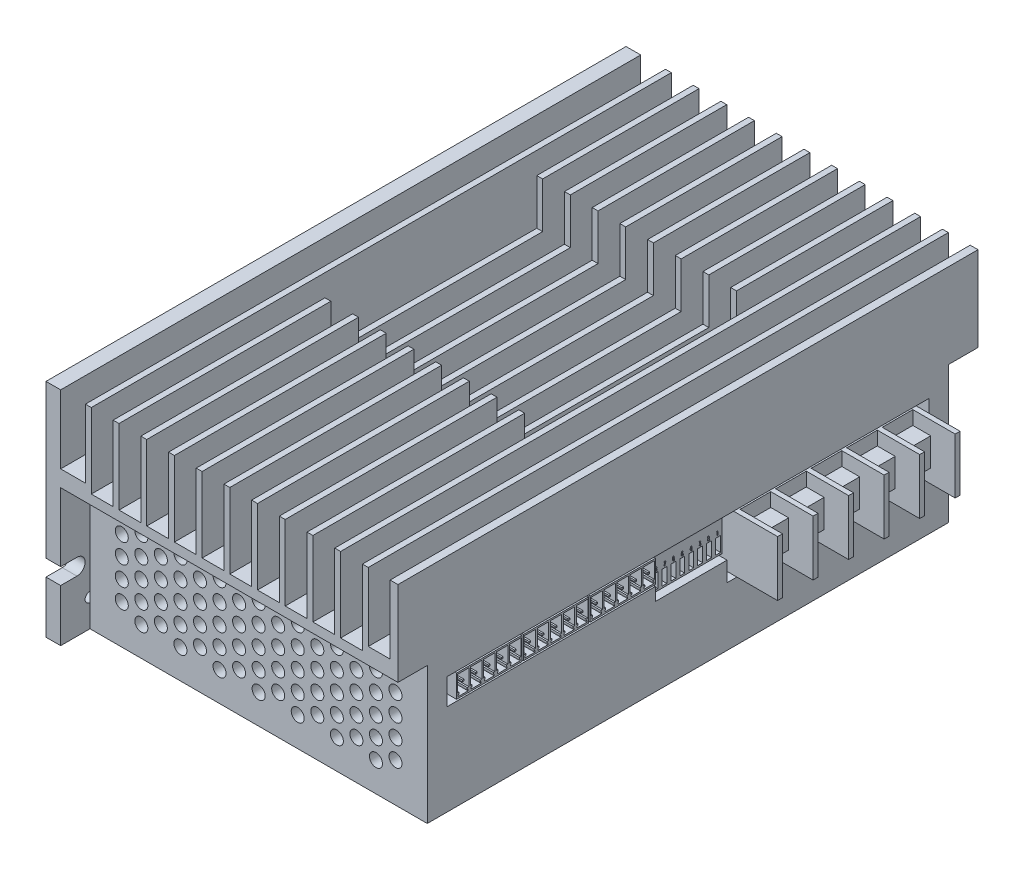
SolidWorks part; units mm, degrees
ref_plane "前视基准面" through (0, 0, 0) normal (0, 0, 1) x (1, 0, 0)
ref_plane "上视基准面" through (0, 0, 0) normal (0, 1, 0) x (1, 0, 0)
ref_plane "右视基准面" through (0, 0, 0) normal (1, 0, 0) x (0, 0, -1)
other "Configuration Table"
sketch "草图1" plane through (0, 0, 0) normal (0, 0, 1) x (1, 0, 0)
  line L0 (-49.5, -34) -> (-49.5, 8)
  line L1 (-54, 34) -> (54, 34)
  line L2 (-54, 34) -> (-54, -34)
  line L3 (-54, -34) -> (54, -34)
  line L4 (54, 34) -> (54, -34)
  line L5 (-54, 34) -> (54, -34) construction
  line L6 (-54, -34) -> (54, 34) construction
  line L7 (-49.5, 8) -> (54, 8)
  line L8 (-49.5, 13) -> (-49.5, 34)
  line L10 (-41, 38.0786) -> (-41, 9.5056) construction
  line L11 (-41.9, 13) -> (-41.9, 34)
  line L12 (-40.1, 11) -> (-40.1, 34)
  line L13 (-33.4, 11) -> (-33.4, 34)
  line L14 (-32.5, 38.0786) -> (-32.5, 9.5056) construction
  line L15 (-31.6, 11) -> (-31.6, 34)
  line L16 (-24.9, 11) -> (-24.9, 34)
  line L18 (-23.1, 11) -> (-23.1, 34)
  line L19 (-16.4, 11) -> (-16.4, 34)
  line L21 (-14.6, 11) -> (-14.6, 34)
  line L22 (-7.9, 11) -> (-7.9, 34)
  line L24 (-6.1, 11) -> (-6.1, 34)
  line L25 (0.6, 11) -> (0.6, 34)
  line L27 (2.4, 11) -> (2.4, 34)
  line L28 (9.1, 11) -> (9.1, 34)
  line L30 (10.9, 11) -> (10.9, 34)
  line L31 (17.6, 11) -> (17.6, 34)
  line L33 (19.4, 11) -> (19.4, 34)
  line L34 (26.1, 11) -> (26.1, 34)
  line L36 (27.9, 11) -> (27.9, 34)
  line L37 (34.6, 11) -> (34.6, 34)
  line L39 (36.4, 11) -> (36.4, 34)
  line L40 (43.1, 11) -> (43.1, 34)
  line L42 (44.9, 13) -> (44.9, 34)
  line L43 (51.6, 13) -> (51.6, 34)
  line L46 (-49.5, 13) -> (-41.9, 13)
  line L47 (44.9, 13) -> (51.6, 13)
  line L48 (36.4, 11) -> (43.1, 11)
  line L49 (27.9, 11) -> (34.6, 11)
  line L50 (19.4, 11) -> (26.1, 11)
  line L51 (10.9, 11) -> (17.6, 11)
  line L52 (2.4, 11) -> (9.1, 11)
  line L53 (-6.1, 11) -> (0.6, 11)
  line L54 (-14.6, 11) -> (-7.9, 11)
  line L55 (-23.1, 11) -> (-16.4, 11)
  line L56 (-31.6, 11) -> (-24.9, 11)
  line L71 (-40.1, 11) -> (-33.4, 11)
  line L72 (53.4, 33.6222) -> (53.4, 34) [skipped]
  line L73 (52.5, 38.0786) -> (52.5, 9.5056) construction
  line L74 (44, 38.0786) -> (44, 9.5056) construction
  line L75 (35.5, 38.0786) -> (35.5, 9.5056) construction
  line L76 (27, 38.0786) -> (27, 9.5056) construction
  line L77 (18.5, 38.0786) -> (18.5, 9.5056) construction
  line L78 (10, 38.0786) -> (10, 9.5056) construction
  line L79 (1.5, 38.0786) -> (1.5, 9.5056) construction
  line L80 (-7, 38.0786) -> (-7, 9.5056) construction
  line L81 (-15.5, 38.0786) -> (-15.5, 9.5056) construction
  line L82 (-24, 38.0786) -> (-24, 9.5056) construction
  point P0 (0, 0)
  dimension "D1" = 108
  dimension "D2" = 68
  dimension "D3" = 4.5
  dimension "D4" = 5
  dimension "D5" = 8.5
  dimension "D7" = 42
  dimension "D8" = 23
  dimension "D9" = 12
  dimension "D10" = 8.5
  dimension "D6" = 1.8
extrude "凸台-拉伸1" add sketch "草图1" against normal mid plane 178 contours L71 L12 L1 L11 L46 L8 L2 L3 L0 L7 L4 L43 L47 L42 L40 L48 L39 L37 L49 L36 L34 L50 L33 L31 L51 L30 L28 L52 L27 L25 L53 L24 L22 L54 L21 L19 L55 L18 L16 L56 region at (-51.75, -32.7238, 0)
extrude "凸台-拉伸3" add sketch "草图1<4>" along normal mid plane 160 contours L7 L0 L3 L4 region at (2.25, -13, 0)
sketch "草图1<4>" plane through (0, 0, 0) normal (0, 0, 1) x (1, 0, 0) same geometry as "草图1"
sketch "草图2" plane through (0, 34, 0) normal (0, 1, 0) x (1, 0, 0)
  line L0 (27.9, 89) -> (27.9, -89) construction
  line L1 (-33.4, 89) -> (-33.4, -89) construction
  line L2 (27.9, 41) -> (27.9, -24)
  line L3 (-33.4, 41) -> (-33.4, -24)
  line L4 (-33.4, -24) -> (27.9, -24)
  line L5 (-33.4, 41) -> (27.9, 41)
  line L6 (-6.1, -89) -> (0.6, -89) construction
  dimension "D1" = 65
  dimension "D2" = 65
extrude "切除-拉伸1" cut sketch "草图2" against normal blind 14
sketch "草图3" plane through (0, 0, 80) normal (0, 0, 1) x (1, 0, 0)
  line L0 (-49.5, -13) -> (54, -13) construction
  line L1 (-49.5, -34) -> (-49.5, 8) construction
  line L2 (54, 8) -> (54, -34) construction
  line L3 (2.25, -34) -> (2.25, 8) construction
  line L4 (-49.5, -34) -> (54, -34) construction
  line L5 (-49.5, 8) -> (54, 8) construction
  line L6 (-9.75, -34) -> (-9.75, 8) construction
  line L7 (-21.75, -34) -> (-21.75, 8) construction
  line L8 (-33.75, -34) -> (-33.75, 8) construction
  circle A0 centre (2.25, -13) radius 2
  circle A1 centre (2.25, -7) radius 2
  circle A2 centre (2.25, -19) radius 2
  circle A3 centre (2.25, -1) radius 2
  circle A4 centre (2.25, -25) radius 2
  circle A5 centre (8.25, -10) radius 2
  circle A6 centre (8.25, -16) radius 2
  circle A7 centre (8.25, -4) radius 2
  circle A8 centre (8.25, -22) radius 2
  circle A9 centre (14.25, -1) radius 2
  circle A10 centre (14.25, -7) radius 2
  circle A11 centre (14.25, -13) radius 2
  circle A12 centre (14.25, -19) radius 2
  circle A13 centre (14.25, -25) radius 2
  circle A14 centre (26.25, -1) radius 2
  circle A15 centre (26.25, -7) radius 2
  circle A16 centre (26.25, -13) radius 2
  circle A17 centre (26.25, -19) radius 2
  circle A18 centre (26.25, -25) radius 2
  circle A19 centre (38.25, -1) radius 2
  circle A20 centre (38.25, -7) radius 2
  circle A21 centre (38.25, -13) radius 2
  circle A22 centre (38.25, -19) radius 2
  circle A23 centre (38.25, -25) radius 2
  circle A24 centre (-9.75, -1) radius 2
  circle A25 centre (-9.75, -7) radius 2
  circle A26 centre (-9.75, -13) radius 2
  circle A27 centre (-9.75, -19) radius 2
  circle A28 centre (-9.75, -25) radius 2
  circle A29 centre (-21.75, -1) radius 2
  circle A30 centre (-21.75, -7) radius 2
  circle A31 centre (-21.75, -13) radius 2
  circle A32 centre (-21.75, -19) radius 2
  circle A33 centre (-21.75, -25) radius 2
  circle A34 centre (-33.75, -1) radius 2
  circle A35 centre (-33.75, -7) radius 2
  circle A36 centre (-33.75, -13) radius 2
  circle A37 centre (-33.75, -19) radius 2
  circle A38 centre (-33.75, -25) radius 2
  circle A39 centre (20.25, -4) radius 2
  circle A40 centre (20.25, -10) radius 2
  circle A41 centre (20.25, -16) radius 2
  circle A42 centre (20.25, -22) radius 2
  circle A43 centre (32.25, -4) radius 2
  circle A44 centre (32.25, -10) radius 2
  circle A45 centre (32.25, -16) radius 2
  circle A46 centre (32.25, -22) radius 2
  circle A47 centre (44.25, -4) radius 2
  circle A48 centre (44.25, -10) radius 2
  circle A49 centre (44.25, -16) radius 2
  circle A50 centre (44.25, -22) radius 2
  circle A51 centre (-3.75, -4) radius 2
  circle A52 centre (-3.75, -10) radius 2
  circle A53 centre (-3.75, -16) radius 2
  circle A54 centre (-3.75, -22) radius 2
  circle A55 centre (-15.75, -4) radius 2
  circle A56 centre (-15.75, -10) radius 2
  circle A57 centre (-15.75, -16) radius 2
  circle A58 centre (-15.75, -22) radius 2
  circle A59 centre (-27.75, -4) radius 2
  circle A60 centre (-27.75, -10) radius 2
  circle A61 centre (-27.75, -16) radius 2
  circle A62 centre (-27.75, -22) radius 2
  circle A63 centre (-39.75, -4) radius 2
  circle A64 centre (-39.75, -10) radius 2
  circle A65 centre (-39.75, -16) radius 2
  circle A66 centre (-39.75, -22) radius 2
  dimension "D1" = 4
  dimension "D3" = 12
  dimension "D2" = 6
  dimension "D4" = 6
  dimension "D5" = 6
  dimension "D6" = 6
  dimension "D7" = 4
  dimension "D8" = 4
extrude "切除-拉伸2" cut sketch "草图3" against normal through all
sketch "草图4" plane through (-54, 0, 0) normal (-1, 0, 0) x (0, 0, 1)
  line L0 (-102.5637, -15.5) -> (106.9046, -15.5) construction
  line L1 (-89, -34) -> (89, -34) construction
  line L2 (84, -13) -> (89, -13)
  line L3 (89, 34) -> (89, -34) construction
  line L4 (84, -18) -> (89, -18)
  line L5 (0, 12.214) -> (0, -19.2786) construction
  line L6 (-84, -18) -> (-89, -18)
  line L7 (-84, -13) -> (-89, -13)
  line L8 (80, -34) -> (80, 8) construction
  line L9 (80, -34) -> (80, 8) construction
  arc A0 (84, -13) -> (84, -18) centre (84, -15.5) ccw
  arc A1 (-84, -13) -> (-84, -18) centre (-84, -15.5) cw
  circle A2 centre (80, -25.5) radius 1.5
  circle A3 centre (-80, -25.5) radius 1.5
  line M3 (89, -34) -> (89, 34)
  line M5 (-89, 34) -> (-89, -34)
  dimension "D2" = 5
  dimension "D4" = 3
  dimension "D1" = 18.5
  dimension "D3" = 5
  dimension "D5" = 10
extrude "切除-拉伸3" cut sketch "草图4" along direction (1, 0, 0) on the side against the normal up to vertex (4.5 mm away) contours L2 A0 L4 M3 | A2 | A3 | A1 L7 L6 M5 region at (-54, -15.5, 85.4959) region at (-54, -15.5, -85.4959) region at (-54, -25.5, 80) region at (-54, -25.5, -80) up to point (-49.5, 8, 89)
sketch "草图5" plane through (54, 0, 0) normal (1, 0, 0) x (0, 0, -1)
  line L0 (-74, 2) -> (74, 2)
  line L1 (74, 2) -> (74, -16)
  line L2 (74, -16) -> (12, -16)
  line L3 (12, -16) -> (12, -10)
  line L4 (12, -10) -> (-10, -10)
  line L5 (-10, -10) -> (-10, -6)
  line L6 (-10, -6) -> (-74, -6)
  line L7 (-74, -6) -> (-74, 2)
  line L9 (80, 8) -> (80, -34) construction
  line L10 (-80, 8) -> (-80, -34) construction
  line L11 (-80, 8) -> (-89, 8) construction
  dimension "D1" = 6
  dimension "D2" = 6
  dimension "D3" = 6
  dimension "D4" = 8
  dimension "D5" = 12
  dimension "D6" = 18
  dimension "D7" = 64
  dimension "D8" = 22
extrude "切除-拉伸4" cut sketch "草图5" against normal blind 5
sketch "草图7" plane through (49, 0, 0) normal (1, 0, 0) x (0, 0, -1)
  line L0 (-10, -6) -> (-10, -10) construction
  line L1 (-10, -5.5) -> (-30, -5.5)
  line L2 (-10, -5.5) -> (-10, 1.5)
  line L3 (-10, 1.5) -> (-30, 1.5)
  line L4 (-30, -5.5) -> (-30, 1.5)
  line L5 (-74, -6) -> (-10, -6) construction
  line L6 (74, 2) -> (-74, 2) construction
  line L7 (-10, -10) -> (12, -10) construction
  line L8 (-30.5, -5.5) -> (-50.5, -5.5)
  line L9 (-30.5, -5.5) -> (-30.5, 1.5)
  line L10 (-30.5, 1.5) -> (-50.5, 1.5)
  line L11 (-50.5, -5.5) -> (-50.5, 1.5)
  line L12 (-51, -5.5) -> (-71, -5.5)
  line L13 (-51, -5.5) -> (-51, 1.5)
  line L14 (-51, 1.5) -> (-71, 1.5)
  line L15 (-71, -5.5) -> (-71, 1.5)
  line L16 (-9.5, 1.5) -> (12.5, 1.5)
  line L17 (-9.5, 1.5) -> (-9.5, -9.5)
  line L18 (-9.5, -9.5) -> (12.5, -9.5)
  line L19 (12.5, 1.5) -> (12.5, -9.5)
  line L20 (12, -16) -> (74, -16) construction
  line L21 (14.5, 1.5) -> (70.5, 1.5)
  line L22 (14.5, 1.5) -> (14.5, -15.5)
  line L23 (14.5, -15.5) -> (70.5, -15.5)
  line L24 (70.5, 1.5) -> (70.5, -15.5)
  line L25 (-61, 1.5) -> (-61, -5.5) construction
  line L26 (-62.75, -4) -> (-62.75, 1)
  line L27 (-62.75, 1) -> (-59.25, 1)
  line L28 (-59.25, 1) -> (-59.25, -4)
  line L29 (-59.25, -4) -> (-59.75, -4)
  line L30 (-59.75, -4) -> (-59.75, -4.5)
  line L31 (-59.75, -4.5) -> (-59.4916, -4.5)
  line L32 (-59.4916, -4.5) -> (-59.4916, -5)
  line L33 (-59.4916, -5) -> (-62.5084, -5)
  line L34 (-62.5084, -5) -> (-62.5084, -4.5)
  line L35 (-62.5084, -4.5) -> (-62.25, -4.5)
  line L36 (-62.25, -4.5) -> (-62.25, -4)
  line L37 (-62.25, -4) -> (-62.75, -4)
  line L38 (-62.75, -1.5) -> (-59.25, -1.5) construction
  line L39 (-62.75, -1.5) -> (-71.738, -1.5) construction
  line L40 (-61.25, -1.25) -> (-60.75, -1.25)
  line L41 (-61.25, -1.25) -> (-61.25, -1.75)
  line L42 (-61.25, -1.75) -> (-60.75, -1.75)
  line L43 (-60.75, -1.25) -> (-60.75, -1.75)
  line L44 (-61.25, -1.25) -> (-60.75, -1.75) construction
  line L45 (-61.25, -1.75) -> (-60.75, -1.25) construction
  line L46 (-59.25, -1.5) -> (-51, -1.5) construction
  line L71 (-66.75, 1) -> (-63.25, 1)
  line L72 (-66.75, -4) -> (-66.75, 1)
  line L73 (-66.25, -4) -> (-66.75, -4)
  line L74 (-66.25, -4.5) -> (-66.25, -4)
  line L75 (-66.5084, -4.5) -> (-66.25, -4.5)
  line L76 (-66.5084, -5) -> (-66.5084, -4.5)
  line L77 (-63.4916, -5) -> (-66.5084, -5)
  line L78 (-63.4916, -4.5) -> (-63.4916, -5)
  line L79 (-63.75, -4.5) -> (-63.4916, -4.5)
  line L80 (-63.75, -4) -> (-63.75, -4.5)
  line L81 (-63.25, -4) -> (-63.75, -4)
  line L82 (-63.25, 1) -> (-63.25, -4)
  line L83 (-64.75, -1.25) -> (-64.75, -1.75)
  line L84 (-65.25, -1.75) -> (-64.75, -1.75)
  line L85 (-65.25, -1.25) -> (-65.25, -1.75)
  line L86 (-65.25, -1.25) -> (-64.75, -1.25)
  line L87 (-70.75, 1) -> (-67.25, 1)
  line L88 (-70.75, -4) -> (-70.75, 1)
  line L89 (-70.25, -4) -> (-70.75, -4)
  line L90 (-70.25, -4.5) -> (-70.25, -4)
  line L91 (-70.5084, -4.5) -> (-70.25, -4.5)
  line L92 (-70.5084, -5) -> (-70.5084, -4.5)
  line L93 (-67.4916, -5) -> (-70.5084, -5)
  line L94 (-67.4916, -4.5) -> (-67.4916, -5)
  line L95 (-67.75, -4.5) -> (-67.4916, -4.5)
  line L96 (-67.75, -4) -> (-67.75, -4.5)
  line L97 (-67.25, -4) -> (-67.75, -4)
  line L98 (-67.25, 1) -> (-67.25, -4)
  line L99 (-68.75, -1.25) -> (-68.75, -1.75)
  line L100 (-69.25, -1.75) -> (-68.75, -1.75)
  line L101 (-69.25, -1.25) -> (-69.25, -1.75)
  line L102 (-69.25, -1.25) -> (-68.75, -1.25)
  line L103 (-58.25, -4) -> (-58.75, -4)
  line L104 (-58.75, -4) -> (-58.75, 1)
  line L105 (-58.75, 1) -> (-55.25, 1)
  line L106 (-55.25, 1) -> (-55.25, -4)
  line L107 (-55.25, -4) -> (-55.75, -4)
  line L108 (-55.75, -4) -> (-55.75, -4.5)
  line L109 (-55.75, -4.5) -> (-55.4916, -4.5)
  line L110 (-55.4916, -4.5) -> (-55.4916, -5)
  line L111 (-55.4916, -5) -> (-58.5084, -5)
  line L112 (-58.5084, -5) -> (-58.5084, -4.5)
  line L113 (-58.5084, -4.5) -> (-58.25, -4.5)
  line L114 (-58.25, -4.5) -> (-58.25, -4)
  line L115 (-57.25, -1.25) -> (-57.25, -1.75)
  line L116 (-57.25, -1.25) -> (-56.75, -1.25)
  line L117 (-56.75, -1.25) -> (-56.75, -1.75)
  line L118 (-57.25, -1.75) -> (-56.75, -1.75)
  line L119 (-54.25, -4) -> (-54.75, -4)
  line L120 (-54.75, -4) -> (-54.75, 1)
  line L121 (-54.75, 1) -> (-51.25, 1)
  line L122 (-51.25, 1) -> (-51.25, -4)
  line L123 (-51.25, -4) -> (-51.75, -4)
  line L124 (-51.75, -4) -> (-51.75, -4.5)
  line L125 (-51.75, -4.5) -> (-51.4916, -4.5)
  line L126 (-51.4916, -4.5) -> (-51.4916, -5)
  line L127 (-51.4916, -5) -> (-54.5084, -5)
  line L128 (-54.5084, -5) -> (-54.5084, -4.5)
  line L129 (-54.5084, -4.5) -> (-54.25, -4.5)
  line L130 (-54.25, -4.5) -> (-54.25, -4)
  line L131 (-53.25, -1.25) -> (-53.25, -1.75)
  line L132 (-53.25, -1.25) -> (-52.75, -1.25)
  line L133 (-52.75, -1.25) -> (-52.75, -1.75)
  line L134 (-53.25, -1.75) -> (-52.75, -1.75)
  line L135 (-51, -1.5) -> (-50.5, -1.5) construction
  line L136 (-50.75, -1.5) -> (-50.75, 2.9227) construction
  line L137 (-32.25, -1.25) -> (-32.75, -1.25)
  line L138 (-32.25, -1.25) -> (-32.25, -1.75)
  line L139 (-32.25, -1.75) -> (-32.75, -1.75)
  line L140 (-32.75, -1.25) -> (-32.75, -1.75)
  line L141 (-30.75, -4) -> (-30.75, 1)
  line L142 (-31.25, -4) -> (-30.75, -4)
  line L143 (-31.25, -4.5) -> (-31.25, -4)
  line L144 (-30.9916, -4.5) -> (-31.25, -4.5)
  line L145 (-30.9916, -5) -> (-30.9916, -4.5)
  line L146 (-34.0084, -5) -> (-30.9916, -5)
  line L147 (-34.0084, -4.5) -> (-34.0084, -5)
  line L148 (-33.75, -4.5) -> (-34.0084, -4.5)
  line L149 (-33.75, -4) -> (-33.75, -4.5)
  line L150 (-34.25, -4) -> (-33.75, -4)
  line L151 (-34.25, 1) -> (-34.25, -4)
  line L152 (-30.75, 1) -> (-34.25, 1)
  line L153 (-36.25, -1.25) -> (-36.75, -1.25)
  line L154 (-36.25, -1.25) -> (-36.25, -1.75)
  line L155 (-36.25, -1.75) -> (-36.75, -1.75)
  line L156 (-36.75, -1.25) -> (-36.75, -1.75)
  line L157 (-34.75, -4) -> (-34.75, 1)
  line L158 (-35.25, -4) -> (-34.75, -4)
  line L159 (-35.25, -4.5) -> (-35.25, -4)
  line L160 (-34.9916, -4.5) -> (-35.25, -4.5)
  line L161 (-34.9916, -5) -> (-34.9916, -4.5)
  line L162 (-38.0084, -5) -> (-34.9916, -5)
  line L163 (-38.0084, -4.5) -> (-38.0084, -5)
  line L164 (-37.75, -4.5) -> (-38.0084, -4.5)
  line L165 (-37.75, -4) -> (-37.75, -4.5)
  line L166 (-38.25, -4) -> (-37.75, -4)
  line L167 (-38.25, 1) -> (-38.25, -4)
  line L168 (-34.75, 1) -> (-38.25, 1)
  line L169 (-40.25, -1.75) -> (-40.75, -1.75)
  line L170 (-40.75, -1.25) -> (-40.75, -1.75)
  line L171 (-40.25, -1.25) -> (-40.75, -1.25)
  line L172 (-40.25, -1.25) -> (-40.25, -1.75)
  line L173 (-39.25, -4.5) -> (-39.25, -4)
  line L174 (-38.9916, -4.5) -> (-39.25, -4.5)
  line L175 (-38.9916, -5) -> (-38.9916, -4.5)
  line L176 (-42.0084, -5) -> (-38.9916, -5)
  line L177 (-42.0084, -4.5) -> (-42.0084, -5)
  line L178 (-41.75, -4.5) -> (-42.0084, -4.5)
  line L179 (-41.75, -4) -> (-41.75, -4.5)
  line L180 (-42.25, -4) -> (-41.75, -4)
  line L181 (-42.25, 1) -> (-42.25, -4)
  line L182 (-38.75, 1) -> (-42.25, 1)
  line L183 (-38.75, -4) -> (-38.75, 1)
  line L184 (-39.25, -4) -> (-38.75, -4)
  line L185 (-44.25, -1.25) -> (-44.75, -1.25)
  line L186 (-44.75, -1.25) -> (-44.75, -1.75)
  line L187 (-44.25, -1.75) -> (-44.75, -1.75)
  line L188 (-44.25, -1.25) -> (-44.25, -1.75)
  line L189 (-43.25, -4.5) -> (-43.25, -4)
  line L190 (-42.9916, -4.5) -> (-43.25, -4.5)
  line L191 (-42.9916, -5) -> (-42.9916, -4.5)
  line L192 (-46.0084, -5) -> (-42.9916, -5)
  line L193 (-46.0084, -4.5) -> (-46.0084, -5)
  line L194 (-45.75, -4.5) -> (-46.0084, -4.5)
  line L195 (-45.75, -4) -> (-45.75, -4.5)
  line L196 (-46.25, -4) -> (-45.75, -4)
  line L197 (-46.25, 1) -> (-46.25, -4)
  line L198 (-42.75, 1) -> (-46.25, 1)
  line L199 (-42.75, -4) -> (-42.75, 1)
  line L200 (-43.25, -4) -> (-42.75, -4)
  line L201 (-48.25, -1.25) -> (-48.75, -1.25)
  line L202 (-48.75, -1.25) -> (-48.75, -1.75)
  line L203 (-48.25, -1.75) -> (-48.75, -1.75)
  line L204 (-48.25, -1.25) -> (-48.25, -1.75)
  line L205 (-47.25, -4.5) -> (-47.25, -4)
  line L206 (-46.9916, -4.5) -> (-47.25, -4.5)
  line L207 (-46.9916, -5) -> (-46.9916, -4.5)
  line L208 (-50.0084, -5) -> (-46.9916, -5)
  line L209 (-50.0084, -4.5) -> (-50.0084, -5)
  line L210 (-49.75, -4.5) -> (-50.0084, -4.5)
  line L211 (-49.75, -4) -> (-49.75, -4.5)
  line L212 (-50.25, -4) -> (-49.75, -4)
  line L213 (-50.25, 1) -> (-50.25, -4)
  line L214 (-46.75, 1) -> (-50.25, 1)
  line L215 (-46.75, -4) -> (-46.75, 1)
  line L216 (-47.25, -4) -> (-46.75, -4)
  line L217 (-30.5, -2) -> (-30, -2) construction
  line L218 (-30.25, -2) -> (-30.25, 3.712) construction
  line L219 (-12.25, -1.25) -> (-12.25, -1.75)
  line L220 (-12.25, -1.75) -> (-11.75, -1.75)
  line L221 (-11.75, -1.25) -> (-11.75, -1.75)
  line L222 (-12.25, -1.25) -> (-11.75, -1.25)
  line L223 (-13.5084, -4.5) -> (-13.25, -4.5)
  line L224 (-13.5084, -5) -> (-13.5084, -4.5)
  line L225 (-10.4916, -5) -> (-13.5084, -5)
  line L226 (-10.4916, -4.5) -> (-10.4916, -5)
  line L227 (-10.75, -4.5) -> (-10.4916, -4.5)
  line L228 (-10.75, -4) -> (-10.75, -4.5)
  line L229 (-10.25, -4) -> (-10.75, -4)
  line L230 (-10.25, 1) -> (-10.25, -4)
  line L231 (-13.75, 1) -> (-10.25, 1)
  line L232 (-13.75, -4) -> (-13.75, 1)
  line L233 (-13.25, -4) -> (-13.75, -4)
  line L234 (-13.25, -4.5) -> (-13.25, -4)
  line L235 (-16.25, -1.25) -> (-16.25, -1.75)
  line L236 (-16.25, -1.75) -> (-15.75, -1.75)
  line L237 (-15.75, -1.25) -> (-15.75, -1.75)
  line L238 (-16.25, -1.25) -> (-15.75, -1.25)
  line L239 (-17.5084, -4.5) -> (-17.25, -4.5)
  line L240 (-17.5084, -5) -> (-17.5084, -4.5)
  line L241 (-14.4916, -5) -> (-17.5084, -5)
  line L242 (-14.4916, -4.5) -> (-14.4916, -5)
  line L243 (-14.75, -4.5) -> (-14.4916, -4.5)
  line L244 (-14.75, -4) -> (-14.75, -4.5)
  line L245 (-14.25, -4) -> (-14.75, -4)
  line L246 (-14.25, 1) -> (-14.25, -4)
  line L247 (-17.75, 1) -> (-14.25, 1)
  line L248 (-17.75, -4) -> (-17.75, 1)
  line L249 (-17.25, -4) -> (-17.75, -4)
  line L250 (-17.25, -4.5) -> (-17.25, -4)
  line L251 (-20.25, -1.25) -> (-20.25, -1.75)
  line L252 (-20.25, -1.25) -> (-19.75, -1.25)
  line L253 (-19.75, -1.25) -> (-19.75, -1.75)
  line L254 (-20.25, -1.75) -> (-19.75, -1.75)
  line L255 (-21.5084, -4.5) -> (-21.25, -4.5)
  line L256 (-21.5084, -5) -> (-21.5084, -4.5)
  line L257 (-18.4916, -5) -> (-21.5084, -5)
  line L258 (-18.4916, -4.5) -> (-18.4916, -5)
  line L259 (-18.75, -4.5) -> (-18.4916, -4.5)
  line L260 (-18.75, -4) -> (-18.75, -4.5)
  line L261 (-18.25, -4) -> (-18.75, -4)
  line L262 (-18.25, 1) -> (-18.25, -4)
  line L263 (-21.75, 1) -> (-18.25, 1)
  line L264 (-21.75, -4) -> (-21.75, 1)
  line L265 (-21.25, -4) -> (-21.75, -4)
  line L266 (-21.25, -4.5) -> (-21.25, -4)
  line L267 (-24.25, -1.25) -> (-24.25, -1.75)
  line L268 (-24.25, -1.75) -> (-23.75, -1.75)
  line L269 (-23.75, -1.25) -> (-23.75, -1.75)
  line L270 (-24.25, -1.25) -> (-23.75, -1.25)
  line L271 (-25.25, -4) -> (-25.75, -4)
  line L272 (-25.25, -4.5) -> (-25.25, -4)
  line L273 (-25.5084, -4.5) -> (-25.25, -4.5)
  line L274 (-25.5084, -5) -> (-25.5084, -4.5)
  line L275 (-22.4916, -5) -> (-25.5084, -5)
  line L276 (-22.4916, -4.5) -> (-22.4916, -5)
  line L277 (-22.75, -4.5) -> (-22.4916, -4.5)
  line L278 (-22.75, -4) -> (-22.75, -4.5)
  line L279 (-22.25, -4) -> (-22.75, -4)
  line L280 (-22.25, 1) -> (-22.25, -4)
  line L281 (-25.75, 1) -> (-22.25, 1)
  line L282 (-25.75, -4) -> (-25.75, 1)
  line L283 (-28.25, -1.25) -> (-28.25, -1.75)
  line L284 (-28.25, -1.75) -> (-27.75, -1.75)
  line L285 (-27.75, -1.25) -> (-27.75, -1.75)
  line L286 (-28.25, -1.25) -> (-27.75, -1.25)
  line L287 (-29.25, -4) -> (-29.75, -4)
  line L288 (-29.25, -4.5) -> (-29.25, -4)
  line L289 (-29.5084, -4.5) -> (-29.25, -4.5)
  line L290 (-29.5084, -5) -> (-29.5084, -4.5)
  line L291 (-26.4916, -5) -> (-29.5084, -5)
  line L292 (-26.4916, -4.5) -> (-26.4916, -5)
  line L293 (-26.75, -4.5) -> (-26.4916, -4.5)
  line L294 (-26.75, -4) -> (-26.75, -4.5)
  line L295 (-26.25, -4) -> (-26.75, -4)
  line L296 (-26.25, 1) -> (-26.25, -4)
  line L297 (-29.75, 1) -> (-26.25, 1)
  line L298 (-29.75, -4) -> (-29.75, 1)
  point P36 (-61, -5)
  point P47 (-61, -1.5)
  dimension "D1" = 20
  dimension "D2" = 0.5
  dimension "D3" = 0.5
  dimension "D4" = 0.5
  dimension "D5" = 0.5
  dimension "D6" = 0.5
  dimension "D7" = 0.5
  dimension "D8" = 22
  dimension "D9" = 2
  dimension "D10" = 56
  dimension "D11" = 0.5
  dimension "D12" = 3.5
  dimension "D13" = 0.5
  dimension "D14" = 0.5
  dimension "D15" = 0.5
  dimension "D16" = 0.5
  dimension "D17" = 0.5
  dimension "D18" = 0.5
  dimension "D19" = 3
  dimension "D20" = 3
extrude "凸台-拉伸4" add sketch "草图7" along normal up to surface (5 mm away) contours L15 L12 L13 L14 L36 L37 L26 L27 L28 L29 L30 L31 L32 L33 L34 L35 L71 L82 L81 L80 L79 L78 L77 L76 L75 L74 L73 L72 L87 L98 L97 L96 L95 L94 L93 L92 L91 L90 L89 L88 L113 L114 L103 L104 L105 L106 L107 | L43 L40 L41 L42 | L115 L118 L117 L116 | L131 L134 L133 L132 | L11 L8 L9 L10 L216 L205 L206 L207 L208 L209 L210 L211 L212 L213 L214 L215 L200 L189 L190 L191 L192 L193 L194 L195 L196 L197 L198 L199 L184 L173 L174 L175 L176 L177 L178 L179 L180 L181 L182 L183 L168 L157 L158 L159 L160 L161 L162 | L4 L1 L2 L3 L271 L282 L281 L280 L279 L278 L277 L276 L275 L274 L273 L272 L239 L250 L249 L248 L247 L246 L245 L244 L243 L242 L241 L240 L223 L234 L233 L232 L231 L230 L229 L228 L227 L226 L225 L224 L255 L266 L265 L264 L263 L262 L261 | L204 L201 L202 L203 | L172 L171 L170 L169 | L270 L267 L268 L269 | L238 L235 L236 L237 | L222 L219 L220 L221 | L102 L99 L100 L101 | L86 L83 L84 L85 | L186 L187 L188 L185 | L154 L155 L156 L153 | L140 L139 L138 L137 | L283 L284 L285 L286 | L251 L254 L253 L252 region at (49, -5.2881, 20) region at (49, -5.2881, 40.5) region at (49, -5.2881, 61) region at (49, -1.5, 61) region at (49, -1.5, 57) region at (49, -1.5, 53) region at (49, -1.5, 40.5) region at (49, -1.5, 48.5) region at (49, -1.5, 12) region at (49, -1.5, 16) region at (49, -1.5, 24) up to face at (54, -7.5, -0.5)
extrude "凸台-拉伸5" add sketch "草图7<4>" along normal offset from surface (3 mm away) 2 contours L16 L19 L18 L17 up to face at (54, -7.5, -0.5)
sketch "草图7<4>" plane through (49, 0, 0) normal (1, 0, 0) x (0, 0, -1) same geometry as "草图7"
sketch "草图9" plane through (52, 0, 0) normal (1, 0, 0) x (0, 0, -1)
  line L0 (-9.5, -6.7013) -> (12.5, -6.7013) construction
  line L1 (-9.5, 1.5) -> (-9.5, -9.5) construction
  line L2 (12.5, -9.5) -> (12.5, 1.5) construction
  line L3 (1.5, -6.7013) -> (1.5, -5.0718) construction
  line L4 (2.25, -8.9513) -> (2.25, -4.4513)
  line L13 (-0.5, -8.9513) -> (1, -8.9513)
  line L14 (-0.5, -8.9513) -> (-0.5, -4.4513)
  line L15 (-0.5, -4.4513) -> (1, -4.4513)
  line L16 (1, -8.9513) -> (1, -4.4513)
  line L17 (-0.5, -8.9513) -> (1, -4.4513) construction
  line L18 (-0.5, -4.4513) -> (1, -8.9513) construction
  line L19 (2.25, -8.9513) -> (3.75, -8.9513)
  line L20 (3.75, -8.9513) -> (3.75, -4.4513)
  line L21 (2.25, -4.4513) -> (3.75, -4.4513)
  line L22 (5, -8.9513) -> (5, -4.4513)
  line L23 (5, -8.9513) -> (6.5, -8.9513)
  line L24 (6.5, -8.9513) -> (6.5, -4.4513)
  line L25 (5, -4.4513) -> (6.5, -4.4513)
  line L26 (7.75, -8.9513) -> (7.75, -4.4513)
  line L27 (7.75, -8.9513) -> (9.25, -8.9513)
  line L28 (9.25, -8.9513) -> (9.25, -4.4513)
  line L29 (7.75, -4.4513) -> (9.25, -4.4513)
  line L30 (10.5, -8.9513) -> (10.5, -4.4513)
  line L31 (10.5, -8.9513) -> (12, -8.9513)
  line L32 (12, -8.9513) -> (12, -4.4513)
  line L33 (10.5, -4.4513) -> (12, -4.4513)
  line L34 (-3.25, -8.9513) -> (-3.25, -4.4513)
  line L35 (-3.25, -8.9513) -> (-1.75, -8.9513)
  line L36 (-1.75, -8.9513) -> (-1.75, -4.4513)
  line L37 (-3.25, -4.4513) -> (-1.75, -4.4513)
  line L38 (-6, -8.9513) -> (-6, -4.4513)
  line L39 (-6, -8.9513) -> (-4.5, -8.9513)
  line L40 (-4.5, -8.9513) -> (-4.5, -4.4513)
  line L41 (-6, -4.4513) -> (-4.5, -4.4513)
  line L42 (-8.75, -8.9513) -> (-8.75, -4.4513)
  line L43 (-8.75, -8.9513) -> (-7.25, -8.9513)
  line L44 (-7.25, -8.9513) -> (-7.25, -4.4513)
  line L45 (-8.75, -4.4513) -> (-7.25, -4.4513)
  line L46 (-9.5, -4) -> (12.5, -4) construction
  line L47 (-9.5, -9.5) -> (-9.5, 1.5) construction
  line L48 (12.5, 1.5) -> (12.5, -9.5) construction
  point P8 (0.25, -6.7013)
  dimension "D1" = 1.5
  dimension "D2" = 4.5
  dimension "D3" = 1.25
  dimension "D4" = 5
  dimension "D5" = 4
extrude "切除-拉伸5" cut sketch "草图9" against normal blind 2 contours L45 L42 L43 L44 | L41 L38 L39 L40 | L37 L34 L35 L36 | L13 L16 L15 L14 | L21 L4 L19 L20 | L25 L22 L23 L24 | L29 L26 L27 L28 | L33 L30 L31 L32 | L42 L45 L44 L43 region at (52, -6.7013, -3) region at (52, -6.7013, -0.25) region at (52, -6.7013, -5.75) region at (52, -6.7013, -8.5) region at (52, -6.7013, -11.25) region at (52, -6.7013, 2.5) region at (52, -6.7013, 5.25) region at (52, -6.7013, 8)
sketch "草图11" plane through (52, 0, 0) normal (1, 0, 0) x (0, 0, -1)
  text T0 "8   7   6   5   4   3   2   1" font "汉仪长仿宋体" height 1.3
extrude "凸台-拉伸6" add sketch "草图11" along normal blind 0.25
extrude "凸台-拉伸7" add sketch "草图7<5>" along normal blind 18 contours L24 L21 L22 L23 region at (49, -7, -42.5)
sketch "草图7<5>" plane through (49, 0, 0) normal (1, 0, 0) x (0, 0, -1) same geometry as "草图7"
sketch "草图13" plane through (67, 0, 0) normal (1, 0, 0) x (0, 0, -1)
  line L0 (26.9, -2.7119) -> (26.9, -11.2881)
  line L1 (16, -2.7119) -> (25.4, -2.7119)
  line L2 (16, -2.7119) -> (16, -11.2881)
  line L3 (42.5, 1.5) -> (42.5, -15.5) construction
  line L4 (14.5, 1.5) -> (70.5, 1.5) construction
  line L5 (14.5, -15.5) -> (70.5, -15.5) construction
  line L6 (16, 1.5) -> (16, -15.5)
  line L7 (14.5, 1.5) -> (14.5, -15.5) construction
  line L8 (26.9, 1.5) -> (26.9, -15.5)
  line L9 (37.8, 1.5) -> (37.8, -15.5)
  line L10 (48.7, 1.5) -> (48.7, -15.5)
  line L11 (59.6, 1.5) -> (59.6, -15.5)
  line L12 (70.5, 1.5) -> (70.5, -15.5)
  line L13 (14.5, 1.5) -> (14.5, -15.5)
  line L14 (25.4, 1.5) -> (25.4, -15.5)
  line L15 (36.3, 1.5) -> (36.3, -15.5)
  line L16 (47.2, 1.5) -> (47.2, -15.5)
  line L17 (58.1, 1.5) -> (58.1, -15.5)
  line L18 (69, 1.5) -> (69, -15.5)
  line L19 (16, -7) -> (25.4, -7) construction
  line L20 (16, -11.2881) -> (25.4, -11.2881)
  line L21 (25.4, -2.7119) -> (25.4, -11.2881)
  line L22 (16, -2.7119) -> (25.4, -11.2881) construction
  line L23 (16, -11.2881) -> (25.4, -2.7119) construction
  line L24 (26.9, -2.7119) -> (36.3, -2.7119)
  line L25 (36.3, -2.7119) -> (36.3, -11.2881)
  line L26 (26.9, -11.2881) -> (36.3, -11.2881)
  line L27 (37.8, -2.7119) -> (37.8, -11.2881)
  line L28 (37.8, -2.7119) -> (47.2, -2.7119)
  line L29 (47.2, -2.7119) -> (47.2, -11.2881)
  line L30 (37.8, -11.2881) -> (47.2, -11.2881)
  line L31 (48.7, -2.7119) -> (48.7, -11.2881)
  line L32 (48.7, -2.7119) -> (58.1, -2.7119)
  line L33 (58.1, -2.7119) -> (58.1, -11.2881)
  line L34 (48.7, -11.2881) -> (58.1, -11.2881)
  line L35 (59.6, -2.7119) -> (59.6, -11.2881)
  line L36 (59.6, -2.7119) -> (69, -2.7119)
  line L37 (69, -2.7119) -> (69, -11.2881)
  line L38 (59.6, -11.2881) -> (69, -11.2881)
  point P0 (20.7, -7)
  line M7 (70.5, 1.5) -> (14.5, 1.5)
  line M9 (14.5, -15.5) -> (70.5, -15.5)
  dimension "D1" = 1.5
extrude "切除-拉伸8" cut sketch "草图13" against normal up to surface (13 mm away) contours L38 L11 L18 M9 | L11 L36 L18 M7 | L10 L32 L17 M7 | L34 L10 L17 M9 | L30 L9 L16 M9 | L9 L28 L16 M7 | L8 L24 L15 M7 | L26 L8 L15 M9 | L20 L6 L14 M9 | L14 L6 L1 M7 region at (67, -0.6059, -31.6) region at (67, -13.3941, -31.6) region at (67, -0.6059, -20.7) region at (67, -13.3941, -20.7) region at (67, -0.6059, -42.5) region at (67, -13.3941, -42.5) region at (67, -0.6059, -53.4) region at (67, -13.3941, -53.4) region at (67, -0.6059, -64.3) region at (67, -13.3941, -64.3) up to face at (54, -7.5, -0.5)
extrude "切除-拉伸9" cut sketch "草图13<3>" against normal blind 7.5 contours L11 L38 L18 L36 | L10 L34 L17 L32 | L0 L26 L15 L24 | L9 L30 L16 L28 | L2 L20 L14 L1 region at (67, -7, -31.6) region at (67, -7, -20.7) region at (67, -7, -42.5) region at (67, -7, -53.4) region at (67, -7, -64.3)
sketch "草图13<3>" plane through (67, 0, 0) normal (1, 0, 0) x (0, 0, -1) same geometry as "草图13"
hole_wizard "Ø4.0mm 暗销孔1" positions "草图16" profile "草图15" hole size "Ø4.0" standard "GB"
sketch "草图16" plane through (59.5, 0, 0) normal (1, 0, 0) x (0, 0, -1)
  line L0 (16, -7) -> (25.4, -7) construction
  line L1 (16, -2.7119) -> (16, -11.2881) construction
  line L2 (25.4, -2.7119) -> (25.4, -11.2881) construction
  line L4 (26.9, -7) -> (36.3, -7) construction
  line L5 (26.9, -2.7119) -> (26.9, -11.2881) construction
  line L6 (36.3, -2.7119) -> (36.3, -11.2881) construction
  line L8 (37.8, -7) -> (47.2, -7) construction
  line L9 (37.8, 1.5) -> (37.8, -15.5) construction
  line L10 (47.2, 1.5) -> (47.2, -15.5) construction
  line L12 (48.7, -7) -> (58.1, -7) construction
  line L13 (48.7, 1.5) -> (48.7, -15.5) construction
  line L14 (58.1, 1.5) -> (58.1, -15.5) construction
  line L16 (59.6, -7) -> (69, -7) construction
  line L17 (59.6, 1.5) -> (59.6, -15.5) construction
  line L18 (69, -2.7119) -> (69, -11.2881) construction
  point P0 (20.7, -7)
  point P2 (31.6, -7)
  point P4 (42.5, -7)
  point P6 (53.4, -7)
  point P8 (64.3, -7)
  point P51 (20.7, -7)
  point P53 (31.6, -7)
  point P55 (42.5, -7)
  point P57 (53.4, -7)
  point P59 (64.3, -7)
sketch "草图15" plane through (59.5, -7, -20.7) normal (0, 1, 0) x (0, 0, -1)
  line L0 (0, 0) -> (0, 11.3017)
  line L1 (0, 11.3017) -> (2, 10.1)
  line L2 (2, 10.1) -> (2, 0)
  line L5 (2, 0) -> (0, 0)
  line L10 (0, 11.3017) -> (-2, 10.1) construction
  line L11 (0, -6.35) -> (0, 107.95) construction
  dimension "孔直径" = 4
  dimension "孔深度" = 10.1
  dimension "导头角度" = 118
